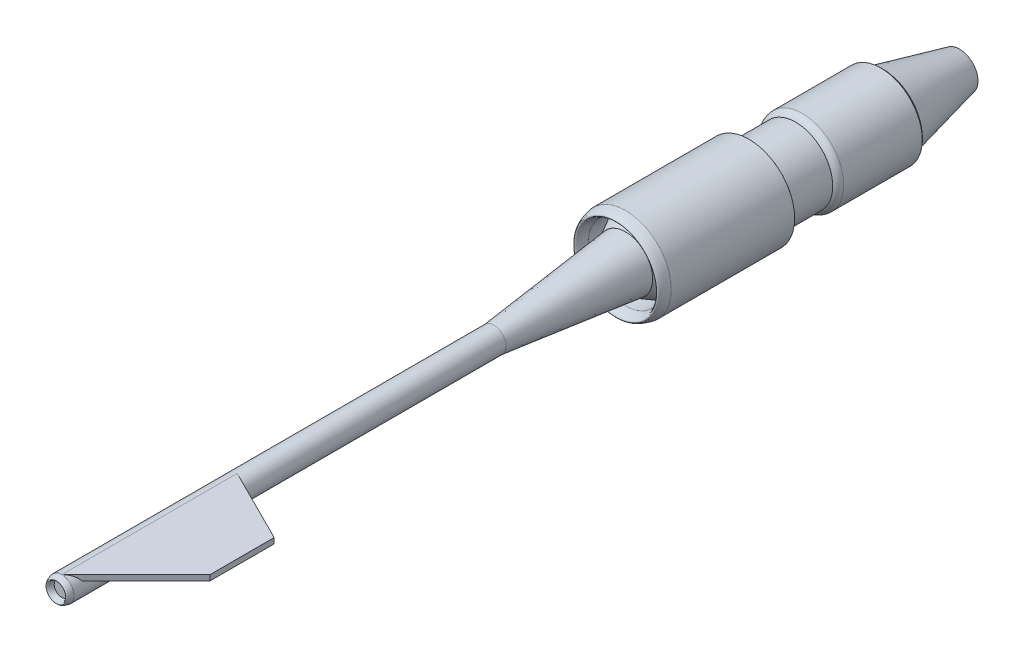
SolidWorks part; units mm, degrees
ref_plane "Front Plane" through (0, 0, 0) normal (0, 0, 1) x (1, 0, 0)
ref_plane "Top Plane" through (0, 0, 0) normal (0, 1, 0) x (1, 0, 0)
ref_plane "Right Plane" through (0, 0, 0) normal (1, 0, 0) x (0, 0, -1)
sketch "Sketch1" plane through (0, 0, 0) normal (0, 0, 1) x (1, 0, 0)
  circle A0 centre (0, 0) radius 416.25
  circle A1 centre (0, 0) radius 337.5
extrude "Boss-Extrude1" add sketch "Sketch1" against normal blind 1125
sketch "Sketch2" plane through (0, 0, 0) normal (1, 0, 0) x (0, 0, -1)
  line L0 (0, 416.25) -> (0, 337.5) construction
  line L1 (0, 337.5) -> (0, 376.875) construction
  line L2 (0, 376.875) -> (-90, 376.875) construction
  line L3 (0, 416.25) -> (0, 337.5)
  line L4 (0, 0) -> (98.8797, 0) construction
  spline S0 degree 2 poles (0, 337.5) (-180, 376.875) (0, 416.25) knots 0 0 0 1 1 1
revolve "Revolve1" add sketch "Sketch2" angle 360 about L4
ref_plane "Plane1" through (0, 0, 0) normal (0, 0, 1) x (1, 0, 0)
sketch "Sketch3" plane through (0, 0, 0) normal (0, 0, 1) x (1, 0, 0)
  circle A0 centre (0, 0) radius 247.5
sketch "Sketch4" plane through (0, 0, 0) normal (0, 1, 0) x (1, 0, 0)
  line L0 (0, 0) -> (0, -1200)
  line L1 (0, -1200) -> (112.5, -1200)
  line L2 (0, 0) -> (247.5, 0)
  line L3 (-247.5, 0) -> (247.5, 0) construction
  line L4 (-457.875, 0) -> (457.875, 0) construction
  line L5 (247.5, 0) -> (112.5, -1200)
revolve "Revolve2" add sketch "Sketch4" angle 360 about L0
sketch "Sketch5" plane through (0, 0, 1200) normal (0, 0, 1) x (1, 0, 0)
  circle A0 centre (0, 0) radius 112.5
extrude "Boss-Extrude2" add sketch "Sketch5" along normal blind 3937.5
sketch "Sketch14" plane through (0, 0, 0) normal (1, 0, 0) x (0, 0, -1)
  line L0 (-5137.5, 112.5) -> (-5137.5, 67.5)
  line L1 (-5137.5, 112.5) -> (-5137.5, -112.5) construction
  line L2 (-5137.5, 67.5) -> (-5137.5, 90)
  line L3 (-5137.5, 90) -> (-5187.5, 90) construction
  line L4 (-5137.5, 0) -> (-5198.2274, 0) construction
  line L5 (-5137.5, 112.5) -> (-5137.5, -112.5) construction
  spline S0 degree 2 poles (-5137.5, 67.5) (-5237.5, 90) (-5137.5, 112.5) knots 0 0 0 1 1 1
  dimension "D1" = 50
  dimension "D2" = 67.5
  dimension "D3" = 90
revolve "Revolve4" add sketch "Sketch14" angle 360 about L4 region at (0, 90, 5157.5)
sketch "Sketch15" plane through (0, 0, -1125) normal (0, 0, -1) x (-1, 0, 0)
  circle A0 centre (0, 0) radius 337.5
extrude "Boss-Extrude5" add sketch "Sketch15" along normal blind 486 separate body
sketch "Sketch16" plane through (0, 0, -1611) normal (0, 0, -1) x (-1, 0, 0)
  line L0 (0, 337.5) -> (0, 416.25) construction
  line L1 (0, 376.875) -> (79.8334, 376.875) construction
  circle A0 centre (0, 0) radius 337.5 construction
  circle A1 centre (0, 0) radius 337.5 construction
  circle A2 centre (0, 0) radius 416.25 construction
  circle A4 centre (0, 0) radius 376.875
extrude "Boss-Extrude6" add sketch "Sketch16" along normal blind 716
sketch "Sketch17" plane through (0, 0, 0) normal (1, 0, 0) x (0, 0, -1)
  line L0 (2327, 0) -> (3043, 0)
  line L1 (2327, -376.875) -> (2327, 376.875) construction
  line L2 (3043, 0) -> (3043, 168.75)
  line L3 (1611, 337.5) -> (2327, 337.5) construction
  line L4 (2327, 0) -> (2327, 337.5)
  line L5 (2327, 337.5) -> (3043, 168.75)
revolve "Revolve5" add sketch "Sketch17" angle 360 about L0
sketch "Sketch18" plane through (0, 0, 0) normal (1, 0, 0) x (0, 0, -1)
  line L0 (0, 247.5) -> (306.6324, 416.25)
  line L1 (1125, 416.25) -> (0, 416.25) construction
  line L2 (0, 247.5) -> (306.6324, 247.5)
  line L3 (306.6324, 247.5) -> (306.6324, 416.25)
  line L4 (0, 0) -> (306.6324, 0) construction
revolve "Revolve6" add sketch "Sketch18" angle 360 about L4
sketch "Sketch19" plane through (0, 0, 0) normal (1, 0, 0) x (0, 0, -1)
  line L1 (1611, 337.5) -> (1611, -337.5) construction
  line L2 (1611, 0) -> (1611, 337.5) construction
  line L3 (1611, 337.5) -> (1551, 337.5)
  line L4 (1611, 0) -> (1571, 0) construction
  line L5 (1611, 337.5) -> (1125, 337.5) construction
  line L6 (1611, 337.5) -> (1611, 376.875)
  line L7 (1611, 376.875) -> (1611, -376.875) construction
  arc A0 (1551, 337.5) -> (1611, 376.875) centre (1614.9642, 305.4325) cw
revolve "Revolve9" add sketch "Sketch19" angle 360 about L4
sketch "Sketch20" plane through (0, 0, 0) normal (1, 0, 0) x (0, 0, -1)
  line L0 (1125, 337.5) -> (1125, 416.25)
  line L1 (1125, 337.5) -> (1155, 337.5)
  line L2 (1551, 337.5) -> (1125, 337.5) construction
  line L3 (1125, 0) -> (1175, 0) construction
  line L4 (1125, -416.25) -> (1125, 416.25) construction
  conic Q0 (1155, 337.5) -> (1125, 416.25) control (1155, 382.5893) rho 0.44632
revolve "Revolve11" add sketch "Sketch20" angle 360 about L3
sketch "Sketch21" plane through (0, 0, 0) normal (1, 0, 0) x (0, 0, -1)
  line L0 (2327, 337.5) -> (2327, 376.875)
  line L1 (2327, 0) -> (2377, 0) construction
  line L2 (2327, -376.875) -> (2327, 376.875) construction
  line L3 (2327, 337.5) -> (2356.2, 330.618)
  line L4 (3043, 168.75) -> (2327, 337.5) construction
  conic Q0 (2327, 376.875) -> (2356.2, 330.618) control (2356.2, 357.1875) rho 0.453502
revolve "Revolve12" add sketch "Sketch21" angle 360 about L1
sketch3d "3DSketch1"
  line L0 (1.7689, 112.4861, 5137.5) -> (-673.2311, 112.4861, 5137.5) construction
  circle A0 centre (0, 0, 5137.5) radius 112.5 construction
  point P2 (0, 0, 5250)
ref_plane "Plane2" through (0, 112.4861, 0) normal (0, 1, 0) x (1, 0, 0)
sketch "Sketch22" plane through (0, 112.4861, 0) normal (0, 1, 0) x (1, 0, 0)
  line L0 (1.7689, -5137.5) -> (1.7689, -3540)
  line L1 (-673.2311, -5137.5) -> (-673.2311, -4462.5) construction
  line L2 (-673.2311, -4462.5) -> (1.7689, -4462.5) construction
  line L3 (-673.2311, -4462.5) -> (1.7689, -5137.5)
  line L4 (-673.2311, -4462.5) -> (-673.2311, -3877.5)
  line L5 (-673.2311, -3877.5) -> (1.7689, -3540)
  line L6 (676.7689, -3877.5) -> (1.7689, -3540)
  line L7 (676.7689, -4462.5) -> (1.7689, -5137.5)
  line L8 (676.7689, -4462.5) -> (676.7689, -3877.5)
extrude "Boss-Extrude7" add sketch "Sketch22" against normal blind 50 contours L7 L8 L6 L0 region at (287.0782, 112.4861, 4267.4227)
